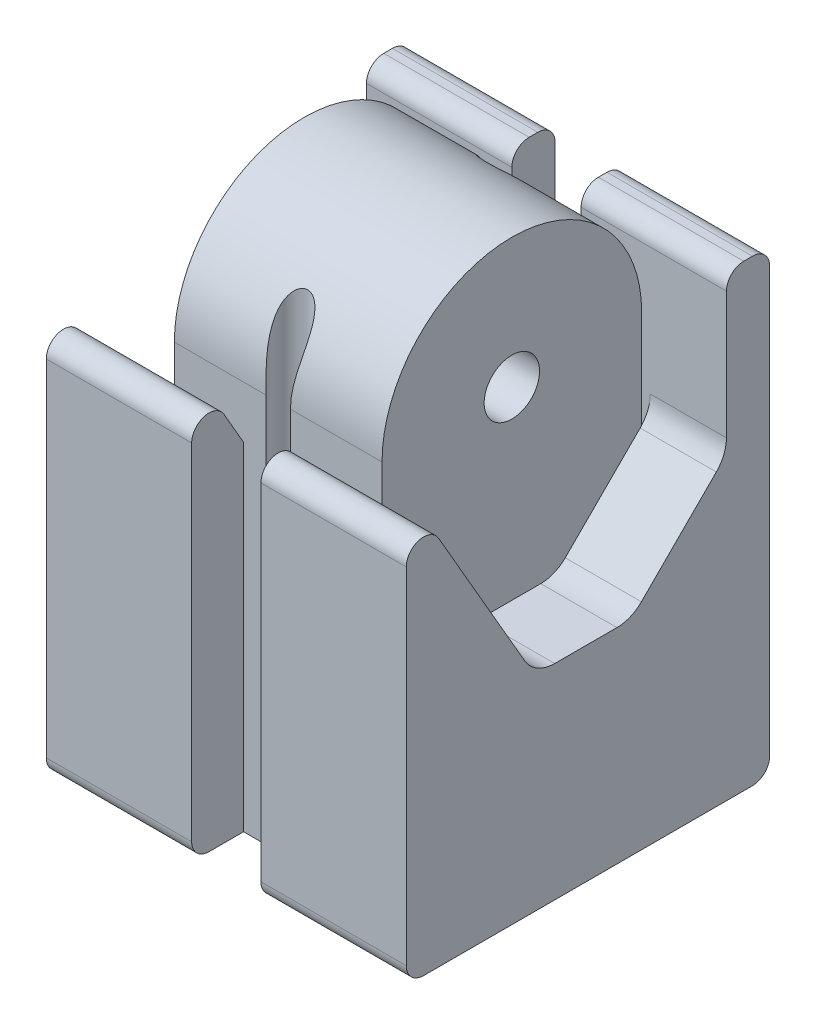
SolidWorks part; units mm, degrees
note: The reader was unsure of these and kept them because the rebuilt part matched: shared geometry of "Sketch2<3>", "Sketch4<4>", "Sketch4<6>".
material "Alloy Steel"
ref_plane "Front Plane" through (0, 0, 0) normal (0, 0, 1) x (1, 0, 0)
ref_plane "Top Plane" through (0, 0, 0) normal (0, 1, 0) x (1, 0, 0)
ref_plane "Right Plane" through (0, 0, 0) normal (1, 0, 0) x (0, 0, -1)
sketch "Sketch1" plane through (0, 0, 0) normal (1, 0, 0) x (0, 0, -1)
  line L1 (7.5, 0) -> (-7.5, 0)
  line L2 (7.5, 0) -> (7.5, 22.5)
  line L3 (7.5, 22.5) -> (-7.5, 22.5)
  line L4 (-7.5, 0) -> (-7.5, 22.5)
  line L5 (7.5, 0) -> (-7.5, 22.5) construction
  line L6 (7.5, 22.5) -> (-7.5, 0) construction
  arc A0 (-7.5, 22.5) -> (7.5, 22.5) centre (0, 22.5) cw
  circle A1 centre (0, 22.5) radius 1.6
  point P0 (0, 11.25)
  dimension "D3" = 3.2
  dimension "D1" = 22.5
  dimension "D2" = 15
extrude "base" add sketch "Sketch1" along normal mid plane 12 contours A1 L3 L4 L1 L2 | A1 L3 A0
sketch "Sketch2" plane through (0, 0, 0) normal (0, -1, 0) x (1, 0, 0)
  line L0 (6, -7.5) -> (-6, -7.5) construction
  line L1 (6, 7.5) -> (-6, 7.5) construction
  line L2 (6, -7.5) -> (-6, -7.5)
  line L3 (6, 7.5) -> (-6, 7.5)
  line L4 (0, 7.5) -> (0, -7.5) construction
  arc A0 (-0.7071, 7.5) -> (0.7071, 7.5) centre (0, 6.7929) ccw
  arc A1 (-1.2021, -7.5) -> (1.2021, -7.5) centre (0, -6.2979) cw
  line M2 (-6, -7.5) -> (6, -7.5)
  line M4 (6, 7.5) -> (-6, 7.5)
  dimension "D1" = 1.7
  dimension "D2" = 1
  dimension "D3" = 90
  dimension "D4" = 90
extrude "PTFE_clamp_3mm_OD" cut sketch "Sketch2" against normal through all contours A1 L4 M2 | L4 A1 L2
extrude "PTFE_clamp_1.6mm_OD" cut sketch "Sketch2<3>" against normal through all contours L3 L4 A0 | L4 A0 M4
sketch "Sketch2<3>" plane through (0, 0, 0) normal (0, -1, 0) x (1, 0, 0) same geometry as "Sketch2"
sketch "Sketch3" plane through (0, 0, 0) normal (0, -1, 0) x (1, 0, 0)
  circle A0 centre (0, 0) radius 2.9
  dimension "D1" = 5.8
extrude "ruthex_m3_insert_hole" cut sketch "Sketch3" against normal blind 8.3
sketch "reference_axis" plane through (0, 0, 0) normal (0, -1, 0) x (1, 0, 0)
  line L0 (-1.2021, -7.5) -> (-1.2021, 7.5) construction
  line L1 (-0.7071, 7.5) -> (-6, 7.5) construction
  line L2 (-1.2021, 7.5) -> (-0.7071, 7.5) construction
  line L3 (-0.7071, 7.5) -> (-0.7071, -7.5) construction
ref_plane "Plane1" through (-1.2021, 0, 0) normal (-1, 0, 0) x (0, 0, 1)
ref_plane "Plane2" through (-0.7071, 0, 0) normal (-1, 0, 0) x (0, 0, 1)
sketch "Sketch4" plane through (-6, 0, 0) normal (-1, 0, 0) x (0, 0, 1)
  line L0 (-7.5, 0) -> (-10.5, 0)
  line L1 (-7.5, 0) -> (-7.5, 26.5)
  line L2 (-10.5, 0) -> (-10.5, 26.5)
  line L3 (-7.5, 22.5) -> (-7.5, 0)
  line L4 (-7.5, 0) -> (7.5, 0)
  line L5 (7.5, 0) -> (7.5, 22.5)
  line L6 (-7.5, 22.5) -> (-7.5, 0)
  line L7 (-7.5, 0) -> (7.5, 0)
  line L8 (7.5, 0) -> (7.5, 22.5)
  line L9 (-7.5, 26.5) -> (-10.5, 26.5)
  line L10 (6.4952, 18.75) -> (10.5, 25.6865) construction
  line L11 (10.5, 25.6865) -> (10.5, 0)
  line L12 (10.5, 0) -> (7.5, 0)
  line L13 (6.4952, 18.75) -> (2.5, 11.8301) construction
  line L14 (2.5, 11.8301) -> (-2.5, 11.8301)
  line L15 (-2.5, 11.8301) -> (-7.5, 16.8301)
  line L16 (0, 22.5) -> (0, 0) construction
  line L17 (10.5, 24.6865) -> (3.0774, 11.8301)
  line L18 (3.0774, 11.8301) -> (2.5, 11.8301)
  line L19 (-8, 26.5) -> (-8, 0)
  line L20 (-7.5, 16.8301) -> (-8, 17.3301)
  circle A0 centre (0, 22.5) radius 7.5 construction
  arc A1 (7.5, 22.5) -> (-7.5, 22.5) centre (0, 22.5) ccw
  arc A2 (7.5, 22.5) -> (-7.5, 22.5) centre (0, 22.5) ccw
  point P5 (6.4952, 18.75)
  line M6 (-7.5, 22.5) -> (-7.5, 0)
  line M7 (-7.5, 0) -> (7.5, 0)
  line M8 (7.5, 0) -> (7.5, 22.5)
  dimension "D5" = 3
  dimension "D6" = 5
  dimension "D7" = 45
  dimension "D8" = 0.5
  dimension "D9" = 0.5
  dimension "D4" = 30
extrude "side_profile" add sketch "Sketch4" along normal blind 4.4 contours L14 L15 L6 L10 L13 M7 M8 | L6 L20 L19 L0
extrude "angle_constraint_back" add sketch "Sketch4<4>" along normal up to surface (4.4 mm away) and the other way blind 4 contours L1 L9 L2 L0 L6 M6
sketch "Sketch4<4>" plane through (-6, 0, 0) normal (-1, 0, 0) x (0, 0, 1) same geometry as "Sketch4"
extrude "angle_constraint_front" add sketch "Sketch4<6>" along normal up to surface (4.4 mm away) and the other way blind 4 contours L12 L11 L10 M8
sketch "Sketch4<6>" plane through (-6, 0, 0) normal (-1, 0, 0) x (0, 0, 1) same geometry as "Sketch4"
fillet "Fillet4" radius 1 5 edges at (-6.2, 0, -10.5) (-6.2, 26.5, -10.5) (-6.2, 0, 10.5) (-6.2, 24.6865, 10.5) (-6.2, 26.5, -8)
fillet "Fillet5" radius 2 3 edges at (-8.2, 11.8301, -2.5) (-8.2, 17.3301, -8) (-8.2, 11.8301, 3.0774)
mirror "Mirror4" about plane through (0, 0, 0) normal (1, 0, 0) of "Fillet5", "Fillet4", "side_profile", "angle_constraint_front", "angle_constraint_back"
equation "\"alpha\"= 90deg'angle for PTFE clamp slot"
equation "\"D3@Sketch2\"=\"alpha\""
equation "\"D4@Sketch2\"=\"alpha\""
equation "\"beta\"= 30deg'mechanical limit angle"
equation "\"D4@Sketch4\"=\"beta\""
equation "\"base_thickness\"= 12mm"
equation "\"total_joint_thickness\"= 20.8mm"
equation "\"d\"= ( \"total_joint_thickness\" - \"base_thickness\" ) / 2"
equation "\"D1@side_profile\" = \"d\""
equation "\"D2\" =  ( \"total_joint_thickness\" - \"base_thickness\" - 3.4 )  / 2"
equation "\"clearance\"= 0.5mm'between this part and the arc of the middle joint"
equation "\"D8@Sketch4\"=\"clearance\""
equation "\"D9@Sketch4\"=\"clearance\""
